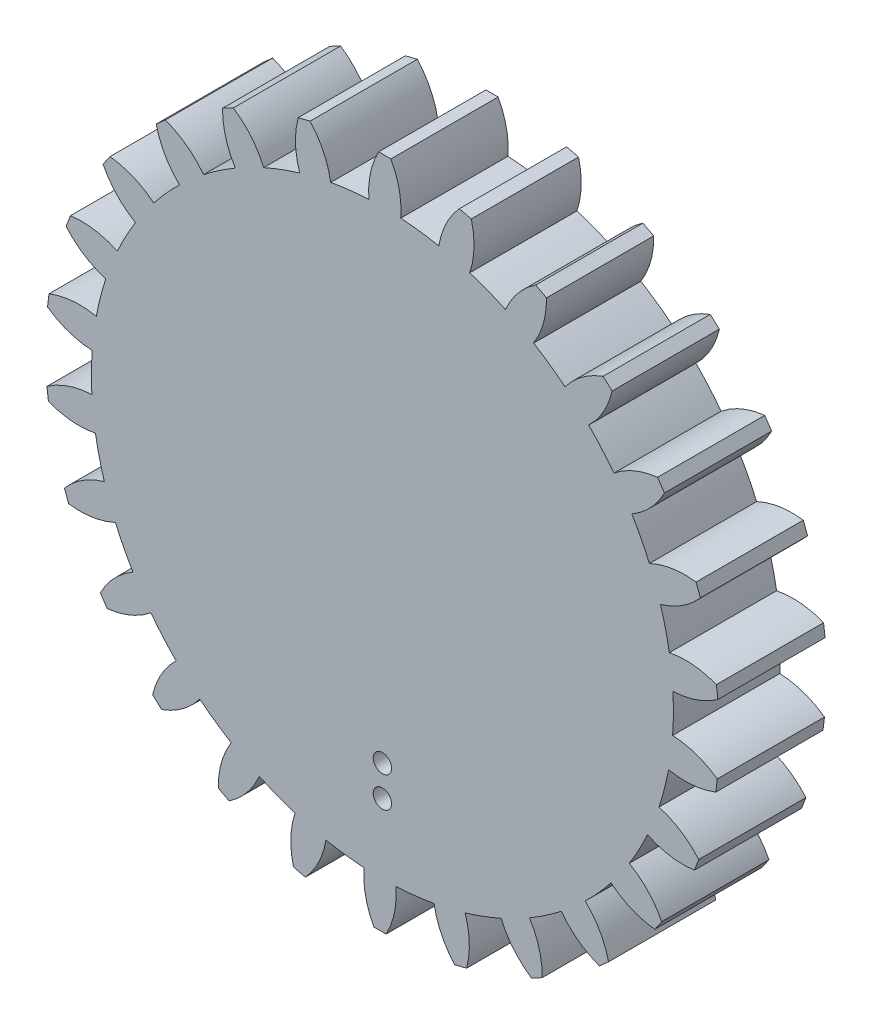
SolidWorks part; units mm, degrees
note: The reader was unsure of these and kept them because the rebuilt part matched: shared geometry of "Sketch1<6>", "Sketch1<7>", "Sketch1<8>".
ref_plane "Front Plane" through (0, 0, 0) normal (0, 0, 1) x (1, 0, 0)
ref_plane "Top Plane" through (0, 0, 0) normal (0, 1, 0) x (1, 0, 0)
ref_plane "Right Plane" through (0, 0, 0) normal (1, 0, 0) x (0, 0, -1)
sketch "Sketch1" plane through (0, 0, 0) normal (0, 0, 1) x (1, 0, 0)
  line L0 (0, 3.5) -> (0, -16.05) construction
  line L3 (-2.65, -2.2864) -> (0, -2.2864)
  line L4 (0, -16.05) -> (0, -14.45) construction
  line L5 (0.2425, -21.995) -> (-0.5575, -21.995)
  line L6 (-2.025, -14.025) -> (-2.65, -2.2864)
  line L7 (0, -2.2864) -> (2.65, -2.2864)
  line L8 (2.025, -14.025) -> (2.65, -2.2864)
  circle A1 centre (0, 0) radius 19
  arc A2 (-2.025, -14.025) -> (2.025, -14.025) centre (0, -14.025) ccw
  arc A5 (2.65, -2.2864) -> (-2.65, -2.2864) centre (0, 0) ccw
  arc A8 (-0.5575, -21.995) -> (-1.197, -18.9623) centre (4.1843, -19.4114) cw
  arc A9 (0.2425, -21.995) -> (0.882, -18.9623) centre (-4.4993, -19.4114) ccw
  circle A10 centre (0, -14.45) radius 0.6
  circle A12 centre (0, -12.45) radius 0.6
  dimension "D1" = 19.55
  dimension "D2" = 38
  dimension "D3" = 2.025
  dimension "D4" = 2
  dimension "D5" = 7
  dimension "D6" = 1.2
  dimension "D7" = 1.2
  dimension "D8" = 1.6
  dimension "D9" = 2.65
extrude "Boss-Extrude2" add sketch "Sketch1" along normal blind 7 contours A1
extrude "Boss-Extrude3" add sketch "Sketch1<6>" along normal blind 7
sketch "Sketch1<6>" plane through (0, 0, 0) normal (0, 0, 1) x (1, 0, 0) same geometry as "Sketch1"
pattern_circular "CirPattern1" count 26 over 360 about axis through (0, 0, 0) along (0, 0, 1) of "Boss-Extrude3"
extrude "Cut-Extrude1" cut sketch "Sketch1<7>" along normal blind 4
sketch "Sketch1<7>" plane through (0, 0, 0) normal (0, 0, 1) x (1, 0, 0) same geometry as "Sketch1"
extrude "Cut-Extrude2" cut sketch "Sketch1<8>" along normal blind 7
sketch "Sketch1<8>" plane through (0, 0, 0) normal (0, 0, 1) x (1, 0, 0) same geometry as "Sketch1"
